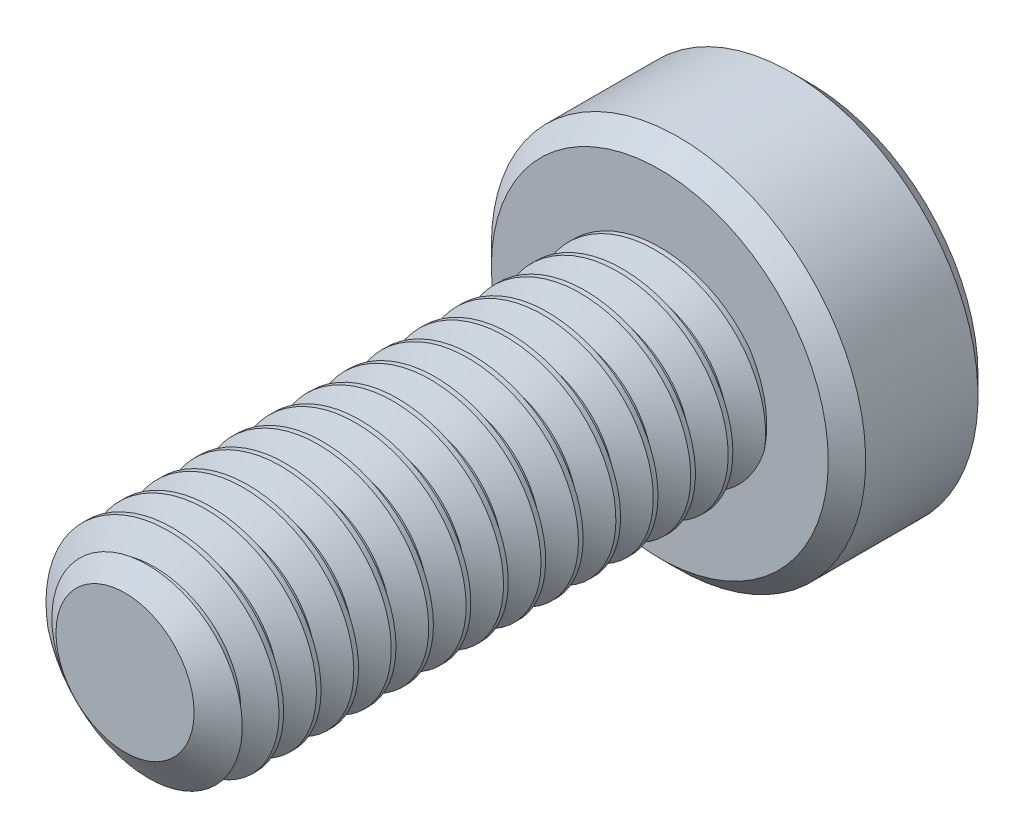
SolidWorks part; units mm, degrees
other "DetailItem1"
ref_plane "Front Plane" through (0, 0, 0) normal (0, 0, 1) x (1, 0, 0)
ref_plane "Top Plane" through (0, 0, 0) normal (0, 1, 0) x (1, 0, 0)
ref_plane "Right Plane" through (0, 0, 0) normal (1, 0, 0) x (0, 0, -1)
sketch "Sketch1" plane through (0, 0, 0) normal (0, 0, 1) x (1, 0, 0)
  circle A0 centre (0, 0) radius 2
  dimension "OD" = 4
extrude "Extrude1" add sketch "Sketch1" against normal blind 10
sketch "Sketch2" plane through (0, 0, 0) normal (0, 0, 1) x (1, 0, 0)
  circle A0 centre (0, 0) radius 2 construction
  circle A1 centre (0, 0) radius 2
curve "Helix/Spiral1" pitch 0.7 height 10.7 radius 2 centre (0, 0, 0) axis (0, 0, -1) start towards (0, 1, 0) parameters "pitch"=0.7
sketch "Sketch3" plane through (0, 0, 0) normal (1, 0, 0) x (0, 0, -1)
  line L0 (-0.6125, 2) -> (-0.35, 1.5453)
  line L1 (-0.35, 1.5453) -> (-0.2625, 1.5453)
  line L2 (-0.2625, 1.5453) -> (0, 2)
  line L3 (-0.6125, 2) -> (0, 2)
  line L4 (-0.3062, 2) -> (-0.3063, 1.5453) construction
  line L5 (-0.4813, 1.7727) -> (-0.1313, 1.7727) construction
  line L6 (0, 2) -> (0, -2) construction
  dimension "D1" = 0.0875
  dimension "D2" = 0.35
  dimension "D3" = 60
sweep "Cut-Sweep1" cut profiles "Sketch3" path "Helix/Spiral1" align with end faces yes
sketch "Sketch4" plane through (0, 0, 0) normal (1, 0, 0) x (0, 0, -1)
  line L0 (0.4962, 2) -> (0, 1.2913)
  line L1 (0, 1.2913) -> (0, 2)
  line L2 (0.4962, 2) -> (0, 2)
  line L3 (-0.6125, 2) -> (0, 2) construction
  line L4 (0, 0) -> (7.0209, 0) construction
  dimension "D1" = 55
  dimension "D2" = 0.254
revolve "Cut-Revolve1" cut sketch "Sketch4" angle 360 about L4
sketch "Sketch6" plane through (0, 0, -10) normal (0, 0, -1) x (-1, 0, 0)
  circle A0 centre (0, 0) radius 3.5
  dimension "head dia" = 7
extrude "Extrude2" add sketch "Sketch6" along normal blind 2.8
sketch "Sketch7" plane through (0, 0, -12.8) normal (0, 0, -1) x (-1, 0, 0)
  line L1 (0, 1.4434) -> (-1.25, 0.7217)
  line L2 (-1.25, 0.7217) -> (-1.25, -0.7217)
  line L3 (-1.25, -0.7217) -> (0, -1.4434)
  line L4 (0, -1.4434) -> (1.25, -0.7217)
  line L5 (1.25, -0.7217) -> (1.25, 0.7217)
  line L6 (1.25, 0.7217) -> (0, 1.4434)
  circle A0 centre (0, 0) radius 1.25 construction
  dimension "hex dia" = 2.5
extrude "Cut-Extrude1" cut sketch "Sketch7" against normal blind 1.875
sketch "Sketch8" plane through (0, 0, -12.8) normal (0, 0, -1) x (-1, 0, 0)
  circle A0 centre (0, 0) radius 1.4434
extrude "Cut-Extrude2" cut sketch "Sketch8" against normal through all draft 45
chamfer "Chamfer1" distance 0.35 angle 45 2 edges at (-3.5, 0, -12.8) (-3.5, 0, -10)
sketch "Sketch10" plane through (0, 0, -10) normal (0, 0, 1) x (1, 0, 0)
  circle A1 centre (0, 0) radius 2
  circle A2 centre (0, 0) radius 2
  dimension "D1" = 0
ref_plane "Plane1" through (0, 0, -30) normal (0, 0, 1) x (1, 0, 0)
extrude "partial thread" [suppressed] add sketch "Sketch10" along normal up to surface (20 mm away) separate body up to plane "Plane1"
chamfer "Chamfer2" [suppressed] distance 0.08 angle 45
combine bodies "Combine1" [suppressed] operation type add bodies to combine 107 108
sketch "Sketch9" plane through (0, 0, 0) normal (1, 0, 0) x (0, 0, -1)
  line L0 (0, 2) -> (0, -2) construction
  line L1 (1.75, 2) -> (1.75, -2) construction
  dimension "D1" = 1.75
equation "\"D3@Helix/Spiral1\" = \"screw length@Extrude1\"+\"pitch@Helix/Spiral1\""
equation "\"D1@Sketch3\" = \"pitch@Helix/Spiral1\"*.125"
equation "\"D2@Sketch3\" = \"pitch@Helix/Spiral1\"*.5"
equation "\"D1@Cut-Extrude1\" = \"hex dia@Sketch7\"*.75"
equation "\"D1@Chamfer1\" = \"head dia@Sketch6\"*.05"
equation "\"D1@Sketch9\" = \"pitch@Helix/Spiral1\"*2.5"
equation "\"D1@Chamfer2\"=\"OD@Sketch1\"*.02"
